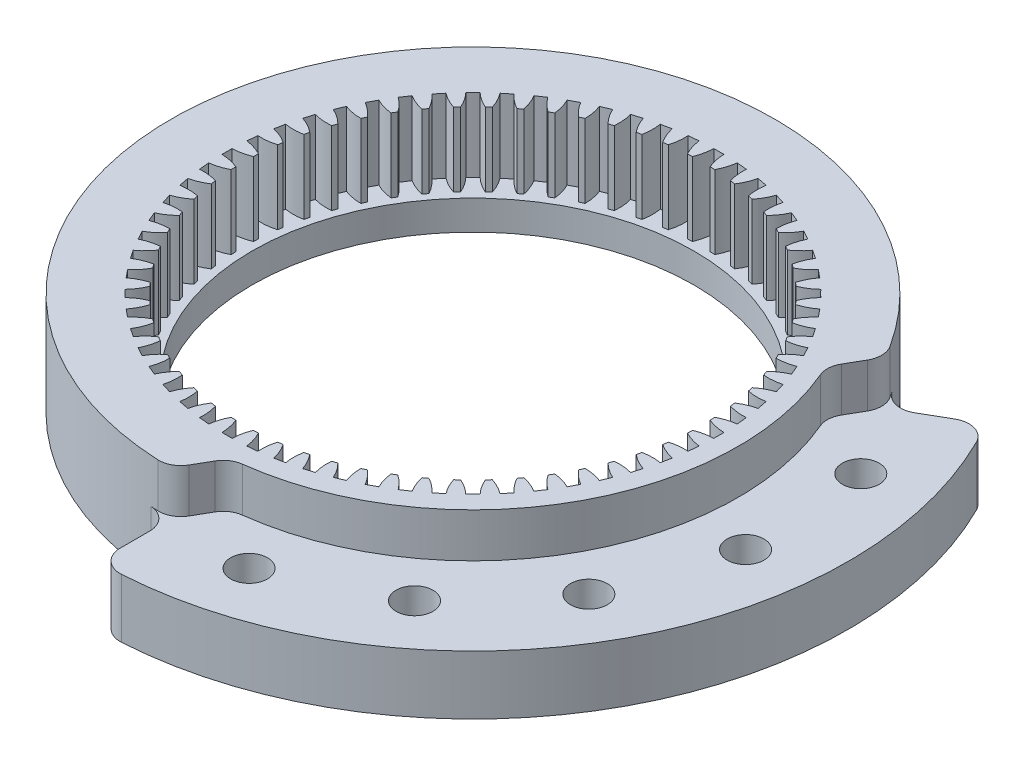
SolidWorks part; units mm, degrees
ref_plane "Front Plane" through (0, 0, 0) normal (0, 0, 1) x (1, 0, 0)
ref_plane "Top Plane" through (0, 0, 0) normal (0, 1, 0) x (1, 0, 0)
ref_plane "Right Plane" through (0, 0, 0) normal (1, 0, 0) x (0, 0, -1)
sketch "Sketch1" plane through (0, 0, 0) normal (0, 1, 0) x (1, 0, 0)
  circle A0 centre (0, 0) radius 16
  circle A1 centre (0, 0) radius 16.7
  circle A2 centre (0, 0) radius 15.5
  dimension "D1" = 32
  dimension "D2" = 33.4
  dimension "D3" = 1.2
extrude "Boss-Extrude1" add sketch "Sketch1" along normal mid plane 5 contours A1 A0 | A0 A2 | A2 region at (-15.5475, 0, 0) region at (-16.2277, 0, 0) region at (0, 0, 0)
sketch "Sketch7" plane through (0, 0, 0) normal (0, 1, 0) x (1, 0, 0)
  line L0 (16.7, 0) -> (-16.7, 0) construction
  line L1 (0, 16.7) -> (0, -16.7) construction
  circle A0 centre (0, 0) radius 16.7 construction
  point P7 (0, 0)
sketch "Sketch4" plane through (0, 0, 0) normal (0, 1, 0) x (1, 0, 0)
  line L0 (0, 0) -> (0, -25.5) construction
  line L10 (0, 0) -> (22.0836, 12.75) construction
  line L11 (22.0836, 12.75) -> (17.7535, 10.25)
  line L12 (0, -25.5) -> (0, -20.5)
  circle A2 centre (0, 0) radius 15.5 construction
  circle A3 centre (0, 0) radius 15.5
  arc A4 (17.7535, 10.25) -> (0, -20.5) centre (0, 0) ccw
  circle A9 centre (0, 0) radius 25.5 construction
  arc A10 (22.0836, 12.75) -> (0, -25.5) centre (0, 0) cw
  dimension "D1" = 5
  dimension "D3" = 120
  dimension "D2" = 5
extrude "Boss-Extrude2" add sketch "Sketch4" along normal mid plane 5
sketch "Sketch3" plane through (0, 0, 0) normal (0, 1, 0) x (1, 0, 0)
  line L0 (0, 0) -> (0, 16.7) construction
  line L1 (-0.3927, 15.9952) -> (0.3927, 15.9952) construction
  line L2 (-0.3434, 15.4962) -> (0, 0) construction
  line L3 (0, 13.7683) -> (-0.5155, 16.692) construction
  line L4 (0, 0) -> (0.8194, 16.6799) construction
  line L5 (0.3927, 15.9952) -> (1.177, 15.9566) construction
  line L6 (0, 15.5) -> (0, 16.7) construction
  line L7 (0.3434, 15.4962) -> (0.3434, 16.7) construction
  line L8 (0.3434, 16.0981) -> (-0.3121, 16.0981) construction
  arc A1 (-0.5957, 16.6894) -> (-0.3434, 15.4962) centre (-3.6364, 15.4232) cw construction
  arc A2 (0.5957, 16.6894) -> (0.3434, 15.4962) centre (3.6364, 15.4232) ccw construction
  circle A3 centre (0, 0) radius 15.5 construction
  arc A4 (0.3434, 15.4962) -> (-0.3434, 15.4962) centre (0, 0) ccw construction
  circle A5 centre (0, 0) radius 16 construction
  circle A6 centre (0, 0) radius 16.7 construction
  arc A7 (0.5957, 15.5068) -> (-0.5957, 15.5068) centre (0, 32.1962) cw
  arc A8 (0.5957, 16.6894) -> (-0.5957, 16.6894) centre (0, 0) ccw construction
  arc A9 (-0.5957, 15.5068) -> (-0.3434, 16.7) centre (-3.6364, 16.773) ccw
  arc A10 (0.5957, 15.5068) -> (0.3434, 16.7) centre (3.6364, 16.773) cw
  arc A11 (0.3434, 16.7) -> (-0.3434, 16.7) centre (0, 32.1962) cw
  dimension "D3" = 2.813
  dimension "D2" = 10
extrude "Cut-Extrude1" cut sketch "Sketch3" against normal through all both and the other way through all
pattern_circular "CirPattern1" count 64 over 360 about axis through (0, 2.5, 0) along (0, 1, 0) of "Cut-Extrude1"
sketch "Sketch5" plane through (0, 0, 0) normal (0, 1, 0) x (1, 0, 0)
  circle A0 centre (0, 0) radius 15.5183
extrude "Cut-Extrude2" cut sketch "Sketch5" against normal through all both and the other way through all
sketch "Sketch8" plane through (0, -2.5, 0) normal (0, -1, 0) x (1, 0, 0)
  line L2 (0, 25.5) -> (0, 20.5)
  line L6 (0, 25.5) -> (0, 20.5)
  line L8 (17.7535, -10.25) -> (22.0836, -12.75)
  line L9 (17.7535, -10.25) -> (22.0836, -12.75)
  circle A0 centre (0, 0) radius 15
  arc A3 (22.0836, -12.75) -> (0, 25.5) centre (0, 0) ccw
  arc A4 (22.0836, -12.75) -> (0, 25.5) centre (0, 0) ccw
  arc A5 (0, 20.5) -> (17.7535, -10.25) centre (0, 0) ccw
  arc A7 (0, 20.5) -> (17.7535, -10.25) centre (0, 0) ccw
  dimension "D2" = 30
  dimension "D1" = 0
extrude "Boss-Extrude3" add sketch "Sketch8" along normal blind 2
sketch "Sketch6" plane through (0, 2.5, 0) normal (0, 1, 0) x (1, 0, 0)
  line L0 (0, 0) -> (5.5646, -20.7674) construction
  line L2 (0, -16.7) -> (0, 16.7) construction
  circle A3 centre (5.5646, -20.7674) radius 0.5
  point P11 (0, 0)
  dimension "D2" = 15
  dimension "D1" = 1
  dimension "D3" = 21.5
extrude "Cut-Extrude3" cut sketch "Sketch6" against normal through all
pattern_circular "CirPattern2" count 5 every 22.5 about axis through (0, -2.5, 0) along (0, -1, 0) of "Cut-Extrude3" reverse direction yes
sketch "Sketch9" plane through (0, 2.5, 0) normal (0, 1, 0) x (1, 0, 0)
  line L0 (17.7535, 10.25) -> (16.275, 7.6892)
  line L1 (0, -20.5) -> (1.4785, -17.9392)
  line L2 (0, 0) -> (18.6195, -10.75) construction
  line L3 (1.4785, -17.9392) -> (16.275, 7.6892) construction
  line L4 (17.7535, 10.25) -> (22.0836, 12.75)
  line L5 (0, -20.5) -> (0, -25.5)
  arc A0 (1.4785, -17.9392) -> (16.275, 7.6892) centre (0, 0) ccw
  arc A1 (0, -25.5) -> (22.0836, 12.75) centre (0, 0) ccw construction
  arc A2 (0, -25.5) -> (22.0836, 12.75) centre (0, 0) ccw
  point P5 (8.8768, -5.125)
  dimension "D1" = 36
extrude "Cut-Extrude4" cut sketch "Sketch9" against normal offset from surface (3 mm away) 4 up to face at (13.2797, -4.5, 17.519)
fillet "Fillet1" radius 1.5 6 edges at (17.7535, -2.5, -10.25) (22.0836, -2.5, -12.75) (0, -2.5, 25.5) (0, -2.5, 20.5) (16.275, 1, -7.6892) (1.4785, 1, 17.9392)
fillet "Fillet2" radius 1.5 2 edges at (0, 1, 20.5) (17.7535, 1, -10.25)
hole_wizard "Ø2.5mm Dowel Hole1" positions "Sketch12" profile "Sketch11" hole size "Ø2.5" standard "ISO"
sketch "Sketch12" plane through (0, -4.5, 0) normal (0, -1, 0) x (-1, 0, 0)
  point P0 (-5.5646, -20.7674)
  point P3 (-13.0884, -17.0571)
  point P6 (-18.6195, -10.75)
  point P9 (-21.3161, -2.8063)
  point P12 (-20.7674, 5.5646)
sketch "Sketch11" plane through (5.5646, -4.5, 20.7674) normal (1, 0, 0) x (0, 0, -1)
  line L0 (0, 0) -> (0, 4.7511)
  line L1 (0, 4.7511) -> (1.25, 4)
  line L2 (1.25, 4) -> (1.25, 0)
  line L5 (1.25, 0) -> (0, 0)
  line L10 (0, 4.7511) -> (-1.25, 4) construction
  line L11 (0, -6.35) -> (0, 107.95) construction
  dimension "Hole Dia." = 2.5
  dimension "Hole Depth" = 4
  dimension "Drill Angle" = 118
ref_axis "Axis2" through (0, -4.5, 0) along (0, 1, 0)
equation "\"Module\"= .5"
equation "\"Number of Teeth\"=64"
equation "\"D1@Sketch1\"=\"Module\"* \"Number of Teeth\""
equation "\"D2@Sketch1\"=(\"Number of Teeth\" + 2) * \"Module\" + .4"
equation "\"D3@Sketch1\"=\"Module\" * if( \"Module\" => 1.25, 2.25, 2.4)"
equation "\"D3@Sketch3\"=180 / \"Number of Teeth\""
equation "\"D1@CirPattern1\"=\"Number of Teeth\""
